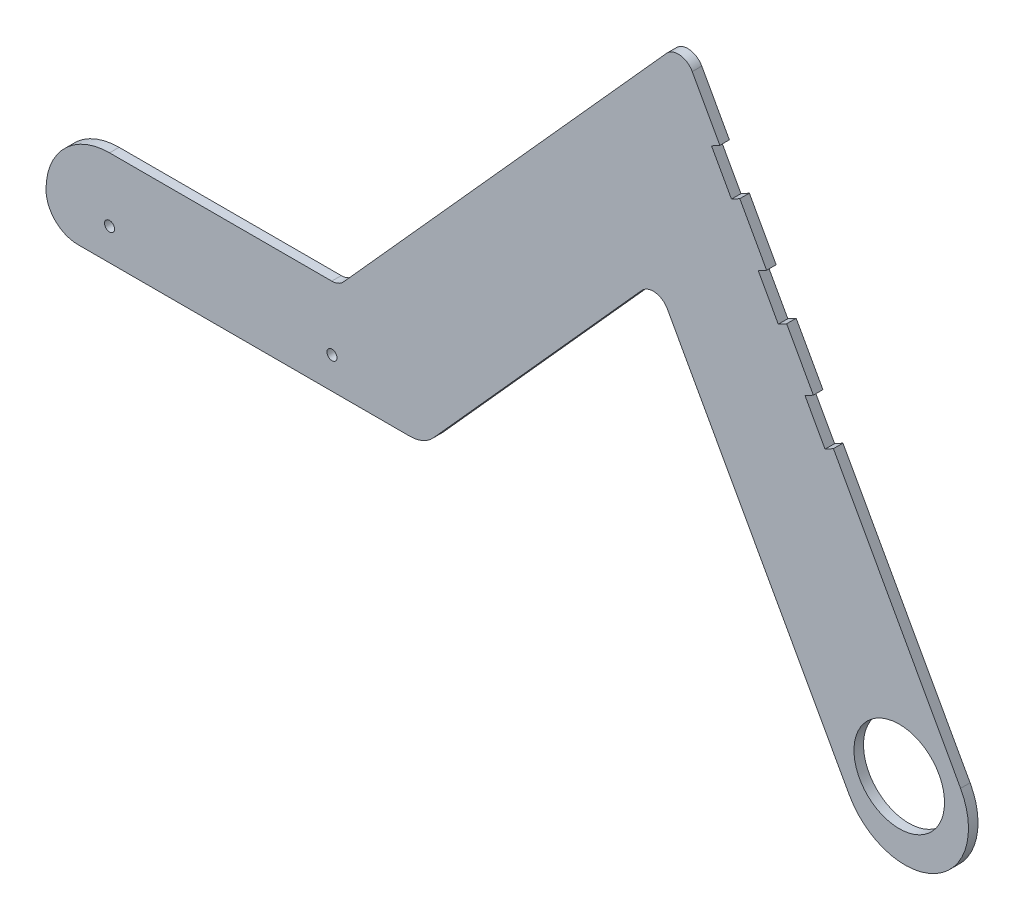
SolidWorks part; units mm, degrees
ref_plane "Front Plane" through (0, 0, 0) normal (0, 0, 1) x (1, 0, 0)
ref_plane "Top Plane" through (0, 0, 0) normal (0, 1, 0) x (1, 0, 0)
ref_plane "Right Plane" through (0, 0, 0) normal (1, 0, 0) x (0, 0, -1)
sketch "Croquis1" plane through (0, 0, 0) normal (0, 0, 1) x (1, 0, 0)
  line L0 (-135.8112, 31.6609) -> (-65.8732, 31.6609)
  line L1 (-62.1542, 33.3189) -> (39.488, 146.4297)
  line L2 (47.5853, 145.5024) -> (132.0431, -7.6343)
  line L3 (97.017, -26.9519) -> (39.7313, 76.9171)
  line L4 (31.634, 77.8443) -> (-44.3213, -6.6811)
  line L5 (-48.0403, -8.3391) -> (-135.8112, -8.3391)
  arc A0 (132.0431, -7.6343) -> (97.017, -26.9519) centre (114.53, -17.2931) cw
  arc A1 (-135.8112, -8.3391) -> (-135.8112, 31.6609) centre (-135.8112, 11.6609) cw
  circle A3 centre (-135.8112, 11.6609) radius 1.58
  circle A4 centre (-65.8112, 11.5885) radius 1.58
  circle A6 centre (112.7386, -14.0449) radius 14.25
  arc A7 (-62.1542, 33.3189) -> (-65.8732, 31.6609) centre (-65.8732, 36.6609) cw
  arc A8 (47.5853, 145.5024) -> (39.488, 146.4297) centre (43.2071, 143.0877) ccw
  arc A9 (39.7313, 76.9171) -> (31.634, 77.8443) centre (35.353, 74.5024) ccw
  arc A10 (-44.3213, -6.6811) -> (-48.0403, -8.3391) centre (-48.0403, -3.3391) cw
  point P17 (-155.8112, 11.6609)
  point P18 (124.1888, -34.8061)
  point P22 (44.1888, 151.6609)
  point P27 (-45.8112, -8.3391)
  dimension "D10" = 3.16
  dimension "D11" = 28.5
  dimension "D13" = 5
  dimension "D1" = 40
  dimension "D2" = 40
  dimension "D3" = 40
  dimension "D4" = 70
  dimension "D5" = 90
  dimension "D6" = 280
  dimension "D7" = 46.467
  dimension "D8" = 90
  dimension "D9" = 120
  dimension "D12" = 20
extrude "Saliente-Extruir1" add sketch "Croquis1" along normal blind 3
sketch "Croquis3" plane through (98.0182, 54.0589, 0) normal (0.8757, 0.4829, 0) x (0, 0, -1)
  line L0 (-3, -70.4538) -> (-3, 104.4289) construction
  line L1 (-3, 86.4289) -> (0, 86.4289)
  line L2 (-3, 86.4289) -> (-3, 73.4264)
  line L3 (-3, 73.4264) -> (0, 73.4264)
  line L4 (0, 86.4289) -> (0, 73.4264)
  line L5 (0, 86.4289) -> (-3, 86.4289) construction
  line L6 (0, -70.4538) -> (0, 104.4289) construction
  line L7 (0, 55.953) -> (-3, 55.953) construction
  line L8 (-3, 55.953) -> (0, 55.953)
  line L9 (-3, 55.953) -> (-3, 42.9048)
  line L10 (-3, 42.9048) -> (0, 42.9048)
  line L11 (0, 55.953) -> (0, 42.9048)
  line L12 (0, 42.9048) -> (-3, 42.9048) construction
  line L13 (0, 25.4771) -> (-3, 25.4771) construction
  line L14 (-3, 25.4771) -> (0, 25.4771)
  line L15 (-3, 25.4771) -> (-3, 12.4289)
  line L16 (-3, 12.4289) -> (0, 12.4289)
  line L17 (0, 25.4771) -> (0, 12.4289)
  line L18 (0, 12.4289) -> (-3, 12.4289) construction
extrude "Cortar-Extruir1" cut sketch "Croquis3" against normal blind 3
sketch "Croquis4" plane through (0, 0, 3) normal (0, 0, 1) x (1, 0, 0)
  line L1 (-177.2002, -8.3391) -> (-13.5247, -8.3391)
  line L2 (-177.2002, -8.3391) -> (-177.2002, 1.6609)
  line L3 (-177.2002, 1.6609) -> (-13.5247, 1.6609)
  line L4 (-13.5247, -8.3391) -> (-13.5247, 1.6609)
  dimension "D1" = 10
extrude "Cortar-Extruir2" cut sketch "Croquis4" against normal blind 10
fillet "Redondeo1" radius 10 2 edges at (-36.8251, 1.6609, 1.5) (-153.1317, 1.6609, 1.5)
